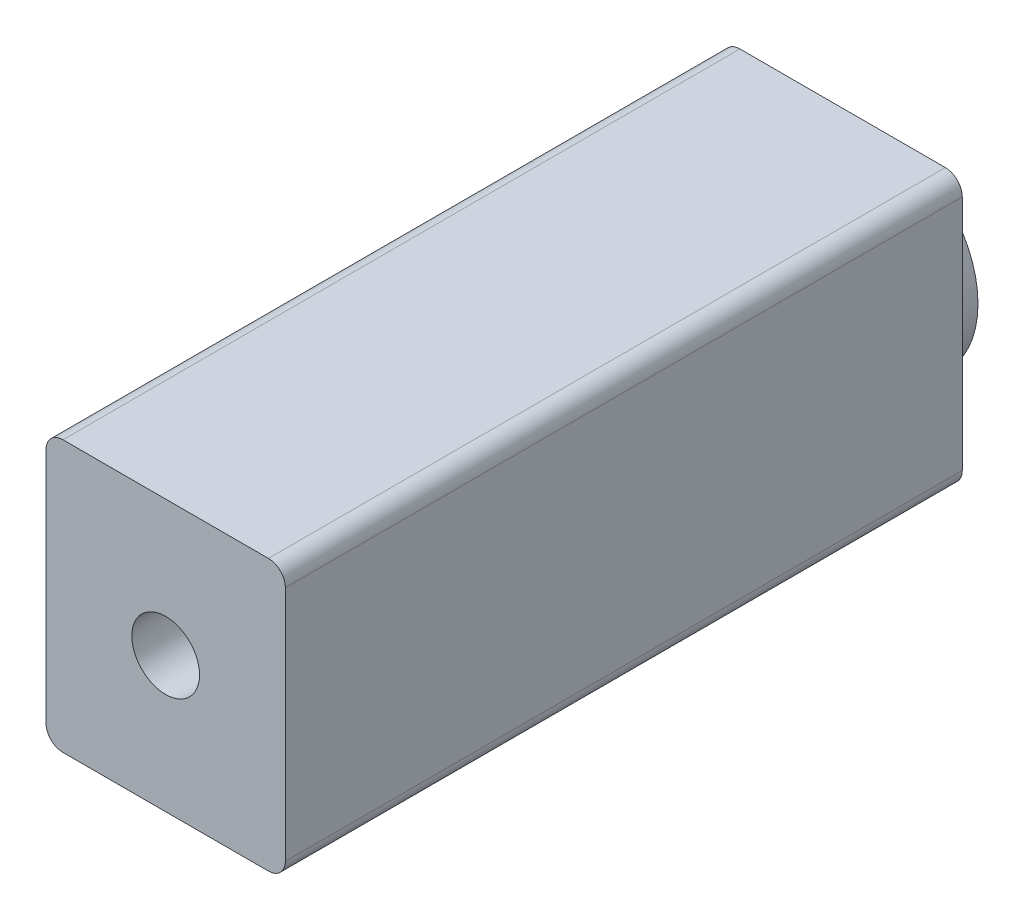
SolidWorks part; units mm, degrees
material "ABS"
ref_plane "Front Plane" through (0, 0, 0) normal (0, 0, 1) x (1, 0, 0)
ref_plane "Top Plane" through (0, 0, 0) normal (0, 1, 0) x (1, 0, 0)
ref_plane "Right Plane" through (0, 0, 0) normal (1, 0, 0) x (0, 0, -1)
sketch "Sketch1" plane through (0, 0, 0) normal (0, 0, 1) x (1, 0, 0)
  circle A0 centre (0, 0) radius 30
  circle A1 centre (0, 0) radius 30 construction
extrude "Boss-Extrude1" add sketch "Sketch1" along normal blind 10
sketch "Sketch2" plane through (0, 0, 10) normal (0, 0, 1) x (1, 0, 0)
  line L0 (35.3553, 40) -> (-35.3553, 40) construction
  line L1 (35.3553, -40) -> (-35.3553, -40)
  line L2 (35.3553, -40) -> (35.3553, 40)
  line L3 (35.3553, 40) -> (-35.3553, 40)
  line L4 (-35.3553, -40) -> (-35.3553, 40)
  line L5 (35.3553, -40) -> (-35.3553, 40) construction
  line L6 (35.3553, 40) -> (-35.3553, -40) construction
  line L7 (35.3553, -35) -> (35.3553, 35) construction
  point P0 (0, 0)
extrude "Boss-Extrude2" add sketch "Sketch2" along normal blind 200
sketch "Sketch3" plane through (0, 0, 210) normal (0, 0, 1) x (1, 0, 0)
  circle A0 centre (0, 0) radius 10
  dimension "D1" = 20
extrude "Cut-Extrude1" cut sketch "Sketch3" against normal blind 150
shell "Shell1" thickness 2
ref_point "Point1"
sketch3d "3DSketch1"
  point P0 (0, 0, 0)
fillet "Fillet1" radius 5 4 edges at (35.3553, 40, 110) (-35.3553, 40, 110) (-35.3553, -40, 110) (35.3553, -40, 110)
ref_plane "Plane1" through (0, 0, 230) normal (0, 0, 1) x (1, 0, 0)
ref_axis "Axis1" through (0, 0, 60) along (0, 0, 1)
ref_point "Point2"
